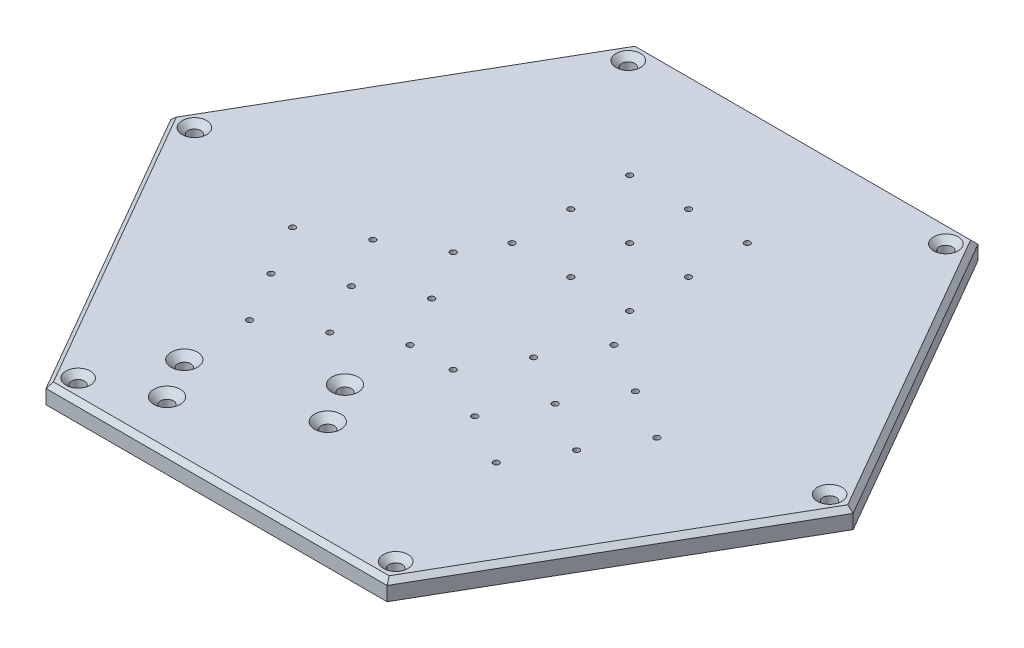
SolidWorks part; units mm, degrees
material "5052-H32"
ref_plane "Front Plane" through (0, 0, 0) normal (0, 0, 1) x (1, 0, 0)
ref_plane "Top Plane" through (0, 0, 0) normal (0, 1, 0) x (1, 0, 0)
ref_plane "Right Plane" through (0, 0, 0) normal (1, 0, 0) x (0, 0, -1)
sketch "Sketch1" plane through (0, 0, 0) normal (0, 1, 0) x (1, 0, 0)
  line L1 (72.5, 125.5737) -> (-72.5, 125.5737)
  line L2 (-72.5, 125.5737) -> (-145, 0)
  line L3 (-145, 0) -> (-72.5, -125.5737)
  line L4 (-72.5, -125.5737) -> (72.5, -125.5737)
  line L5 (72.5, -125.5737) -> (145, 0)
  line L6 (145, 0) -> (72.5, 125.5737)
  circle A0 centre (0, 0) radius 125.5737 construction
  dimension "D1" = 145
extrude "Boss-Extrude1" add sketch "Sketch1" along normal blind 8
sketch "Sketch10" plane through (0, 8, 0) normal (0, 1, 0) x (1, 0, 0)
  line L0 (145, 0) -> (0, 0) construction
  point P4 (135, 0)
  point P7 (67.5, -116.9134)
  point P8 (-67.5, -116.9134)
  point P9 (-135, 0)
  point P10 (-67.5, 116.9134)
  point P11 (67.5, 116.9134)
  point P12 (0, 0)
  dimension "D2" = 10
  dimension "D1" = 6
hole_wizard "CSK for M5 Flat Head Machine Screw2" positions "Sketch14" profile "Sketch13" countersink size "M5" standard "ANSI Metric"
sketch "Sketch14" plane through (0, 8, 0) normal (0, 1, 0) x (1, 0, 0)
  point P0 (-135, 0)
  point P3 (-67.5, -116.9134)
  point P6 (67.5, -116.9134)
  point P9 (135, 0)
  point P12 (67.5, 116.9134)
  point P15 (-67.5, 116.9134)
sketch "Sketch13" plane through (-135, 8, 0) normal (1, 0, 0) x (0, 0, 1)
  line L0 (0, 0) -> (0, 11.6524)
  line L1 (0, 11.6524) -> (2.75, 10)
  line L2 (2.75, 10) -> (2.75, 2.45)
  line L3 (2.75, 2.45) -> (5.2, 0)
  line L5 (5.2, 0) -> (0, 0)
  line L6 (-2.75, 2.45) -> (-5.2, 0) construction
  line L10 (0, 11.6524) -> (-2.75, 10) construction
  line L11 (0, -6.35) -> (0, 107.95) construction
  dimension "Hole Dia." = 5.5
  dimension "Hole Depth" = 10
  dimension "Near C'Sink Dia." = 10.4
  dimension "Near C'Sink Angle" = 90
  dimension "Drill Angle" = 118
chamfer "Chamfer4" distance 2 angle 45 6 edges at (0, 8, 125.5737) (108.75, 8, 62.7868) (108.75, 8, -62.7868) (0, 8, -125.5737) (-108.75, 8, -62.7868) (-108.75, 8, 62.7868)
sketch "Sketch15" plane through (0, 8, 0) normal (0, 1, 0) x (1, 0, 0)
  line L0 (0, 0) -> (21.6506, -12.5) construction
  line L1 (77.4519, -15.8494) -> (52.4519, -59.1506) construction
  line L2 (55.8013, -3.3494) -> (30.8013, -46.6506) construction
  line L3 (34.1506, 9.1506) -> (9.1506, -34.1506) construction
  line L4 (21.6506, -12.5) -> (43.3013, -25) construction
  line L5 (43.3013, -25) -> (64.9519, -37.5) construction
  line L6 (145, 0) -> (0, 0) construction
  point P10 (9.1506, -34.1506)
  point P11 (30.8013, -46.6506)
  point P13 (52.4519, -59.1506)
  point P16 (64.9519, -37.5)
  point P17 (43.3013, -25)
  point P18 (21.6506, -12.5)
  point P19 (34.1506, 9.1506)
  point P20 (55.8013, -3.3494)
  point P21 (77.4519, -15.8494)
  point P23 (-34.1506, 9.1506)
  point P24 (-55.8013, -3.3494)
  point P25 (-77.4519, -15.8494)
  point P26 (-64.9519, -37.5)
  point P27 (-43.3013, -25)
  point P28 (-21.6506, -12.5)
  point P29 (-9.1506, -34.1506)
  point P30 (-30.8013, -46.6506)
  point P31 (-52.4519, -59.1506)
  point P32 (25, 25)
  point P33 (25, 50)
  point P34 (25, 75)
  point P35 (0, 75)
  point P36 (0, 50)
  point P37 (0, 25)
  point P38 (-25, 25)
  point P39 (-25, 50)
  point P40 (-25, 75)
  point P41 (0, 0)
  dimension "D1" = 25
  dimension "D2" = 25
  dimension "D3" = 3
  dimension "D4" = 30
hole_wizard "M3x0.5 Tapped Hole1" positions "Sketch17" profile "Sketch18" tap size "M3x0.5" standard "ANSI Metric"
sketch "Sketch17" plane through (0, 8, 0) normal (0, 1, 0) x (1, 0, 0)
  point P0 (34.1506, 9.1506)
  point P3 (9.1506, -34.1506)
  point P6 (30.8013, -46.6506)
  point P9 (55.8013, -3.3494)
  point P12 (77.4519, -15.8494)
  point P15 (52.4519, -59.1506)
  point P18 (64.9519, -37.5)
  point P21 (43.3013, -25)
  point P24 (21.6506, -12.5)
  point P27 (52.4519, -59.1506)
  point P30 (30.8013, -46.6506)
  point P33 (55.8013, -3.3494)
  point P36 (34.1506, 9.1506)
  point P39 (9.1506, -34.1506)
  point P42 (64.9519, -37.5)
  point P45 (43.3013, -25)
  point P51 (21.6506, -12.5)
  point P55 (-9.1506, -34.1506)
  point P58 (-21.6506, -12.5)
  point P61 (-34.1506, 9.1506)
  point P64 (-55.8013, -3.3494)
  point P67 (-43.3013, -25)
  point P70 (-64.9519, -37.5)
  point P73 (-77.4519, -15.8494)
  point P80 (-30.8013, -46.6506)
  point P83 (-25, 25)
  point P86 (-25, 50)
  point P89 (-25, 75)
  point P92 (0, 75)
  point P95 (0, 50)
  point P98 (0, 25)
  point P101 (25, 25)
  point P104 (25, 50)
  point P107 (-52.4519, -59.1506)
  point P110 (25, 75)
sketch "Sketch18" plane through (34.1506, 8, -9.1506) normal (1, 0, 0) x (0, 0, 1)
  line L0 (0, 0) -> (0, 5.7511)
  line L1 (0, 5.7511) -> (1.25, 5)
  line L2 (1.25, 5) -> (1.25, 0)
  line L5 (1.25, 0) -> (0, 0)
  line L10 (0, 5.7511) -> (-1.25, 5) construction
  line L11 (0, -6.35) -> (0, 107.95) construction
  dimension "Tap Drill Dia." = 2.5
  dimension "Tap Drill Depth" = 5
  dimension "Drill Angle" = 118
cosmetic thread "Hole Thread1" parameters "D1"=4, "D2"=3
cosmetic thread "Hole Thread2" parameters "D1"=4, "D2"=3
cosmetic thread "Hole Thread3" parameters "D1"=4, "D2"=3
cosmetic thread "Hole Thread4" parameters "D1"=4, "D2"=3
cosmetic thread "Hole Thread5" parameters "D1"=4, "D2"=3
cosmetic thread "Hole Thread6" parameters "D1"=4, "D2"=3
cosmetic thread "Hole Thread7" parameters "D1"=4, "D2"=3
cosmetic thread "Hole Thread8" parameters "D1"=4, "D2"=3
cosmetic thread "Hole Thread9" parameters "D1"=4, "D2"=3
cosmetic thread "Hole Thread10" parameters "D1"=4, "D2"=3
cosmetic thread "Hole Thread11" parameters "D1"=4, "D2"=3
cosmetic thread "Hole Thread12" parameters "D1"=4, "D2"=3
cosmetic thread "Hole Thread13" parameters "D1"=4, "D2"=3
cosmetic thread "Hole Thread14" parameters "D1"=4, "D2"=3
cosmetic thread "Hole Thread15" parameters "D1"=4, "D2"=3
cosmetic thread "Hole Thread16" parameters "D1"=4, "D2"=3
cosmetic thread "Hole Thread17" parameters "D1"=4, "D2"=3
cosmetic thread "Hole Thread18" parameters "D1"=4, "D2"=3
cosmetic thread "Hole Thread19" parameters "D1"=4, "D2"=3
cosmetic thread "Hole Thread20" parameters "D1"=4, "D2"=3
cosmetic thread "Hole Thread21" parameters "D1"=4, "D2"=3
cosmetic thread "Hole Thread22" parameters "D1"=4, "D2"=3
cosmetic thread "Hole Thread23" parameters "D1"=4, "D2"=3
cosmetic thread "Hole Thread24" parameters "D1"=4, "D2"=3
cosmetic thread "Hole Thread25" parameters "D1"=4, "D2"=3
cosmetic thread "Hole Thread26" parameters "D1"=4, "D2"=3
cosmetic thread "Hole Thread27" parameters "D1"=4, "D2"=3
sketch "Sketch19" plane through (0, 8, 0) normal (0, -1, 0) x (1, 0, 0)
  line L0 (1.5942, 79.9086) -> (-41.7071, 104.9086) construction
  line L1 (-41.7071, 104.9086) -> (-51.7071, 87.5881) construction
  line L2 (-51.7071, 87.5881) -> (-8.4058, 62.5881) construction
  line L3 (-8.4058, 62.5881) -> (1.5942, 79.9086) construction
  line L4 (-20.0564, 92.4086) -> (-25.0564, 83.7484) construction
  line L5 (-25.0564, 83.7484) -> (-3.4058, 71.2484) construction
  line L6 (-25.0564, 83.7484) -> (-78.75, 114.7484) construction
  line L7 (-145, 0) -> (-72.5, 125.5737) construction
  dimension "D1" = 50
  dimension "D2" = 20
  dimension "D3" = 62
  dimension "D4" = 12.5
hole_wizard "CSK for M5 SFHCS1" positions "Sketch21" profile "Sketch22" countersink size "M5" standard "ANSI Metric"
sketch "Sketch21" plane through (0, 8, 0) normal (0, 1, 0) x (1, 0, 0)
  point P0 (1.5942, -79.9086)
  point P3 (-8.4058, -62.5881)
  point P6 (-51.7071, -87.5881)
  point P9 (-41.7071, -104.9086)
sketch "Sketch22" plane through (1.5942, 8, 79.9086) normal (1, 0, 0) x (0, 0, 1)
  line L0 (0, 0) -> (0, 11.6524)
  line L1 (0, 11.6524) -> (2.75, 10)
  line L2 (2.75, 10) -> (2.75, 2.85)
  line L3 (2.75, 2.85) -> (5.6, 0)
  line L5 (5.6, 0) -> (0, 0)
  line L6 (-2.75, 2.85) -> (-5.6, 0) construction
  line L10 (0, 11.6524) -> (-2.75, 10) construction
  line L11 (0, -6.35) -> (0, 107.95) construction
  dimension "Hole Dia." = 5.5
  dimension "Hole Depth" = 10
  dimension "Near C'Sink Dia." = 11.2
  dimension "Near C'Sink Angle" = 90
  dimension "Drill Angle" = 118
